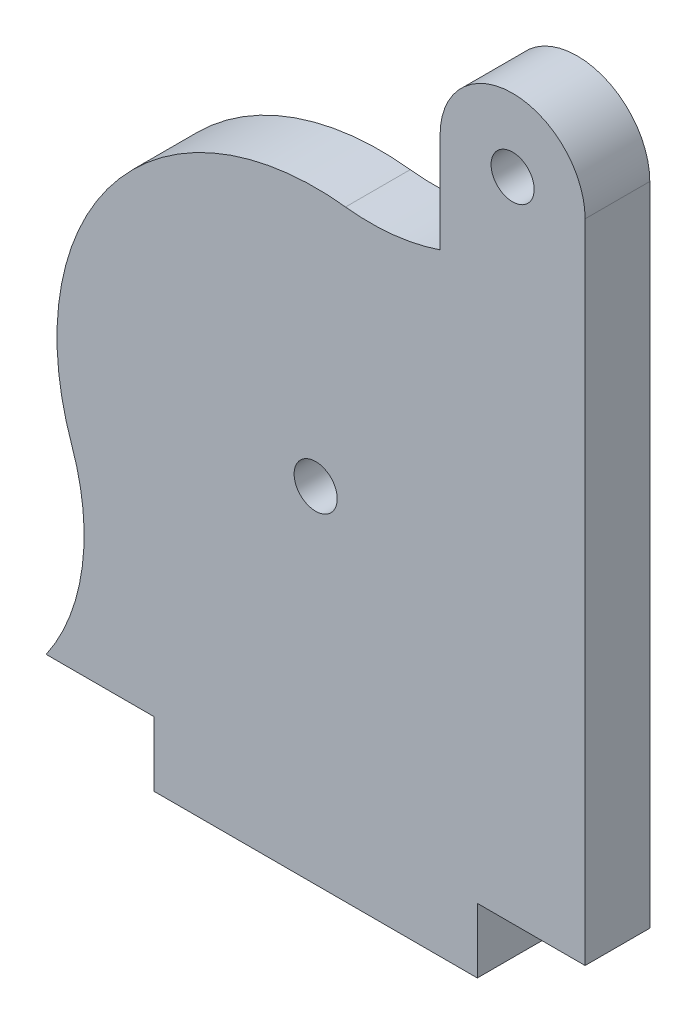
SolidWorks part; units mm, degrees
ref_plane "Front Plane" through (0, 0, 0) normal (0, 0, 1) x (1, 0, 0)
ref_plane "Top Plane" through (0, 0, 0) normal (0, 1, 0) x (1, 0, 0)
ref_plane "Right Plane" through (0, 0, 0) normal (1, 0, 0) x (0, 0, -1)
sketch "Sketch1" plane through (0, 0, 0) normal (0, 0, 1) x (1, 0, 0)
  line L0 (0, 0) -> (5, 0)
  line L1 (5, 0) -> (5, -3)
  line L2 (5, -3) -> (20, -3)
  line L3 (20, -3) -> (20, 0)
  line L4 (20, 0) -> (25, 0)
  line L5 (25, 0) -> (25, 30)
  line L6 (12.5, 35.7928) -> (12.5, -32.0547) construction
  line L7 (18.2713, 30) -> (18.2713, 25.388)
  line L8 (18.2713, 25.388) -> (0, 0) construction
  line L9 (18.2713, 25.388) -> (17.278, 24.0078)
  line L10 (3.5794, 4.9736) -> (0, 0)
  arc A0 (25, 30) -> (18.2713, 30) centre (21.6357, 30) ccw
  circle A1 centre (12.5, 13) radius 1
  circle A2 centre (12.5, 13) radius 8
  arc A3 (17.278, 24.0078) -> (3.5794, 4.9736) centre (12.5, 13) ccw
  circle A4 centre (21.6357, 30) radius 1
  dimension "D1" = 16
  dimension "D2" = 2
  dimension "D7" = 12
  dimension "D8" = 2
  dimension "D3" = 15
  dimension "D4" = 5
  dimension "D5" = 5
  dimension "D6" = 30
  dimension "D9" = 3
  dimension "D10" = 16
extrude "Boss-Extrude1" add sketch "Sketch1" along normal blind 3 contours A2 A1 | L9 A3 L10 L0 L1 L2 L3 L4 L5 A0 L7 A2 region at (2.1479, 2.229, 0) region at (4.7263, 13, 0)
fillet "Fillet2" radius 10 2 edges at (3.5794, 4.9736, 1.5) (17.278, 24.0078, 1.5)
